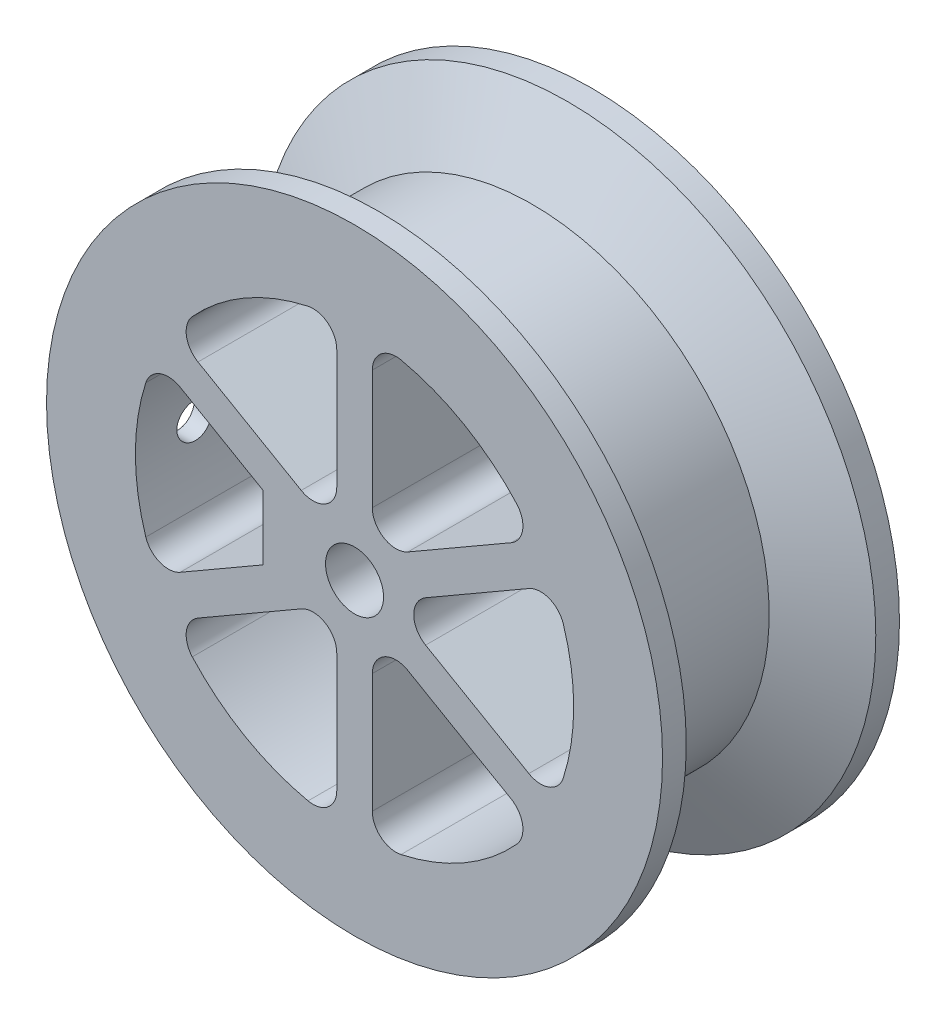
SolidWorks part; units mm, degrees
ref_plane "Front Plane" through (0, 0, 0) normal (0, 0, 1) x (1, 0, 0)
ref_plane "Top Plane" through (0, 0, 0) normal (0, 1, 0) x (1, 0, 0)
ref_plane "Right Plane" through (0, 0, 0) normal (1, 0, 0) x (0, 0, -1)
sketch "Sketch2" plane through (0, 0, 0) normal (0, 1, 0) x (1, 0, 0)
  line L0 (0, 12.7) -> (0, -12.7) construction
  line L1 (0, 12.7) -> (33.02, 12.7)
  line L2 (33.02, 12.7) -> (33.02, 10.16)
  line L3 (33.02, 10.16) -> (25.4, 6.35)
  line L4 (25.4, 6.35) -> (25.4, -10.16)
  line L5 (25.4, -10.16) -> (33.02, -10.16)
  line L6 (33.02, -10.16) -> (33.02, -12.7)
  line L7 (33.02, -12.7) -> (0, -12.7)
  line L8 (0, -12.7) -> (0, 12.7)
  line L9 (0, 0) -> (25.4, 0) construction
  dimension "D1" = 25.4
  dimension "D2" = 2.54
  dimension "D3" = 2.54
  dimension "D4" = 7.62
  dimension "D5" = 33.02
  dimension "D9" = 3.81
revolve "Revolve1" add sketch "Sketch2" angle 360 about L0
sketch "Sketch4" plane through (0, 0, 12.7) normal (0, 0, 1) x (1, 0, 0)
  circle A0 centre (0, 0) radius 3.1115
  dimension "D1" = 6.223
extrude "Cut-Extrude1" cut sketch "Sketch4" against normal through all
sketch "Sketch5" plane through (0, 0, 12.7) normal (0, 0, 1) x (1, 0, 0)
  line L0 (0, 3.175) -> (0, 25.4) construction
  line L1 (2.7496, 1.5875) -> (21.997, 12.7) construction
  line L2 (5.715, 5.4993) -> (16.7821, 11.8888)
  line L3 (1.905, 7.699) -> (1.905, 20.4781)
  line L4 (3.1259, 4.0044) -> (19.3278, 13.3586) construction
  line L5 (1.905, 4.7093) -> (1.905, 23.4176) construction
  arc A1 (0, 25.4) -> (21.997, 12.7) centre (0, 0) cw construction
  arc A2 (2.7496, 1.5875) -> (0, 3.175) centre (0, 0) ccw construction
  arc A3 (4.9838, 22.9603) -> (17.3923, 15.7963) centre (0, 0) cw
  arc A4 (3.1259, 4.0044) -> (1.905, 4.7093) centre (0, 0) ccw
  arc A5 (5.715, 5.4993) -> (1.905, 7.699) centre (4.445, 7.699) cw
  arc A6 (1.905, 23.4176) -> (19.3278, 13.3586) centre (0, 0) cw construction
  arc A7 (4.9838, 22.9603) -> (1.905, 20.4781) centre (4.445, 20.4781) ccw
  arc A8 (17.3923, 15.7963) -> (16.7821, 11.8888) centre (15.5121, 14.0886) cw
  circle A9 centre (0, 0) radius 25.4 construction
  dimension "D3" = 6.35
  dimension "D5" = 2.54
  dimension "D2" = 60
  dimension "D4" = 1.905
extrude "Cut-Extrude2" cut sketch "Sketch5" against normal through all contours A8 A3 A7 L3 A5 L2 | A5 L2 L3 region at (8.2863, 14.3522, 12.7)
pattern_circular "CirPattern1" count 6 over 360 about axis through (0, 0, 12.7) along (0, 0, -1) of "Cut-Extrude2"
sketch "Sketch6" plane through (0, 0, 12.7) normal (0, 0, 1) x (1, 0, 0)
  line L0 (-3.1115, 0) -> (-6.35, 0) construction
  line L2 (-4.7307, -3.4645) -> (-9.8107, -3.4645)
  line L3 (-4.7307, -3.4645) -> (-4.7307, 3.4645)
  line L4 (-4.7307, 3.4645) -> (-9.8107, 3.4645)
  line L5 (-9.8107, -3.4645) -> (-9.8107, 3.4645)
  line L6 (-7.62, 2.1997) -> (-18.6871, 8.5893) construction
  circle A0 centre (0, 0) radius 3.1115 construction
  arc A1 (-7.62, -2.1997) -> (-7.62, 2.1997) centre (-8.89, 0) ccw construction
  point P11 (-4.7307, 0)
  dimension "D1" = 5.08
extrude "Boss-Extrude2" add sketch "Sketch6" against normal through all
hole_wizard "#4 Clearance Hole1" positions "Sketch8" profile "Sketch9" hole size "#4" standard "ANSI Inch"
sketch "Sketch8" plane through (-9.8107, 0, 0) normal (-1, 0, 0) x (0, 0, 1)
  line L0 (-6.35, 0) -> (10.16, 0) construction
  line L1 (-6.35, 25.4) -> (-6.35, -25.4) construction
  line L2 (10.16, 25.4) -> (10.16, -25.4) construction
  point P0 (6.35, 0)
  dimension "D1" = 3.81
sketch "Sketch9" plane through (-9.8107, 0, 6.35) normal (0, 1, 0) x (0, 0, 1)
  line L0 (0, 0) -> (0, 13.7378)
  line L1 (0, 13.7378) -> (1.7272, 12.7)
  line L2 (1.7272, 12.7) -> (1.7272, 0)
  line L5 (1.7272, 0) -> (0, 0)
  line L10 (0, 13.7378) -> (-1.7272, 12.7) construction
  line L11 (0, -6.35) -> (0, 107.95) construction
  dimension "Hole Dia." = 3.4544
  dimension "Hole Depth" = 12.7
  dimension "Drill Angle" = 118
sketch "Sketch10" plane through (-9.8107, 0, 0) normal (-1, 0, 0) x (0, 0, 1)
  circle A0 centre (6.35, 0) radius 1.905
  dimension "D1" = 3.81
extrude "Cut-Extrude3" cut sketch "Sketch10" along normal through all
sketch "Sketch15" plane through (-9.8107, 0, 0) normal (-1, 0, 0) x (0, 0, 1)
  line L0 (6.35, 0) -> (-12.7, 0) construction
  line L1 (-12.7, 33.02) -> (-12.7, -33.02) construction
  line L2 (-12.7, -3.429) -> (8.3297, -3.429)
  line L3 (2.6838, 0) -> (4.5169, -3.175) construction
  line L4 (4.5169, -3.175) -> (8.1831, -3.175) construction
  line L5 (8.1831, -3.175) -> (10.0162, 0) construction
  line L6 (10.0162, 0) -> (8.1831, 3.175) construction
  line L7 (8.1831, 3.175) -> (4.5169, 3.175) construction
  line L8 (4.5169, 3.175) -> (2.6838, 0) construction
  line L9 (8.3297, -3.429) -> (10.3095, 0)
  line L10 (10.3095, 0) -> (8.3297, 3.429)
  line L11 (8.3297, 3.429) -> (-12.7, 3.429)
  line L12 (8.3297, 3.429) -> (4.5169, 3.429) construction
  line L13 (4.5169, -3.429) -> (8.3297, -3.429) construction
  line L14 (-12.7, 3.429) -> (-12.7, -3.429)
  circle A0 centre (6.35, 0) radius 3.175 construction
  dimension "D1" = 6.35
  dimension "D2" = 0.254
extrude "Cut-Extrude7" cut sketch "Sketch15" against normal blind 2.413 from offset 1.778 offset against normal yes
sketch "Sketch13" plane through (0, 0, 0) normal (1, 0, 0) x (0, 0, -1)
  circle A0 centre (0, 0) radius 1
  dimension "D1" = 2
extrude "Cut-Extrude6" [suppressed] cut sketch "Sketch13" along normal through all from offset 25.4
sketch "Sketch16" plane through (0, 0, 0) normal (0, 1, 0) x (1, 0, 0)
  line L0 (0, -12.7) -> (0, 12.7) construction
  line L1 (3.1115, 12.7) -> (-3.1115, 12.7) construction
  line L2 (-33.02, -12.7) -> (33.02, -12.7) construction
  line L3 (0, 5.08) -> (23.495, 12.7)
  line L4 (23.495, 12.7) -> (0, 12.7)
  line L5 (0, 12.7) -> (0, 5.08)
  dimension "D1" = 7.62
revolve "Cut-Revolve1" cut sketch "Sketch16" angle 360 about L0
sketch "Sketch14" plane through (0, 0, 12.7) normal (0, 0, -1) x (-1, 0, 0)
  line L0 (0, 0) -> (33.02, 0) construction
  circle A0 centre (33.02, 0) radius 5.08
  circle A1 centre (0, 0) radius 33.02 construction
  circle A2 centre (0, -33.02) radius 5.08
  circle A3 centre (-33.02, 0) radius 5.08
  circle A4 centre (0, 33.02) radius 5.08
  point P15 (0, 0)
  dimension "D1" = 10.16
  dimension "D2" = 4
extrude "Print Tabs" [suppressed] add sketch "Sketch14" along normal blind 0.4
equation "\"spool_radius\"=1.25"
